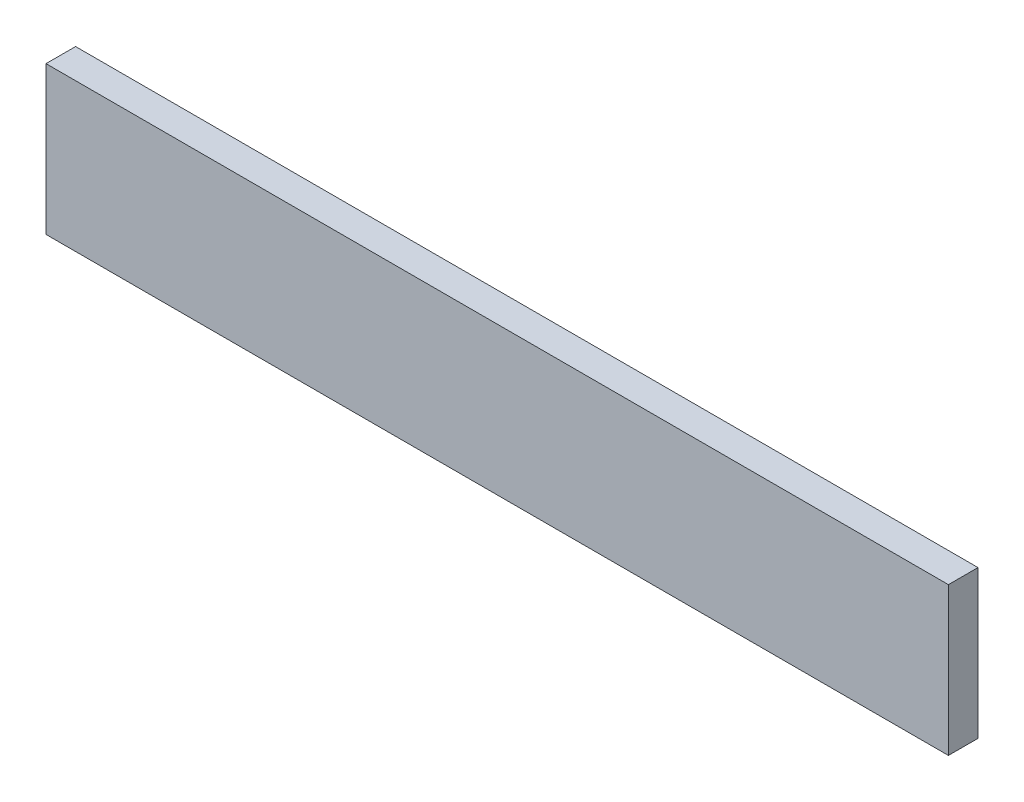
SolidWorks part; units mm, degrees
ref_plane "Ön Düzlem" through (0, 0, 0) normal (0, 0, 1) x (1, 0, 0)
ref_plane "Üst Düzlem" through (0, 0, 0) normal (0, 1, 0) x (1, 0, 0)
ref_plane "Sağ Düzlem" through (0, 0, 0) normal (1, 0, 0) x (0, 0, -1)
sketch "Çizim1" plane through (0, 0, 0) normal (0, 0, 1) x (1, 0, 0)
  line L1 (0, 0) -> (610, 0)
  line L2 (0, 0) -> (0, 100)
  line L3 (0, 100) -> (610, 100)
  line L4 (610, 0) -> (610, 100)
  dimension "D1" = 610
  dimension "D2" = 100
base flange "Taban-Flanş1" sketch "Çizim1" thickness 20 reverse thickness direction no parameters "D1"=4
sketch "Büküm-Çizgileri1" [suppressed] plane through (0, 0, 0) normal (0, 1, 0) x (1, 0, 0)
sketch "Sınırlandırma-Kutusu1" [suppressed] plane through (0, 0, 0) normal (0, 1, 0) x (1, 0, 0)
sheet metal parameters "Sac-Levha1" thickness 20 parameters "D1"=4
flat pattern "Düz-Çoğaltma1" [suppressed]
sketch "Büküm-Çizgileri2" plane through (0, 0, 0) normal (0, 1, 0) x (1, 0, 0)
sketch3d "Sınırlandırma-Kutusu2" [suppressed]
  line L0 (0, 0, 0) -> (610, 0, 0) construction
  line L1 (0, 100, 0) -> (610, 100, 0) construction
  line L2 (0, 0, 0) -> (0, 100, 0) construction
  line L3 (610, 0, 0) -> (610, 100, 0) construction
